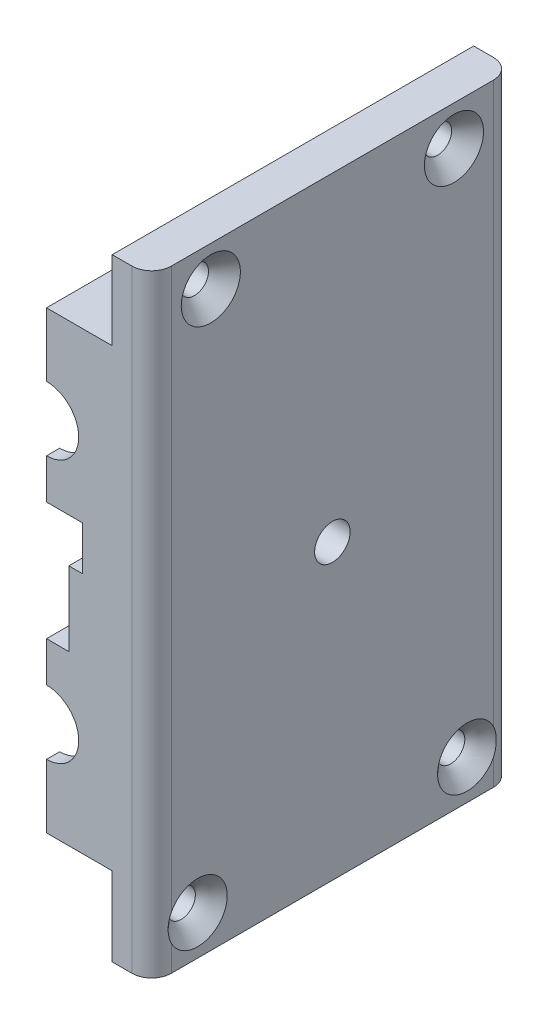
SolidWorks part; units mm, degrees
ref_plane "Front Plane" through (0, 0, 0) normal (0, 0, 1) x (1, 0, 0)
ref_plane "Top Plane" through (0, 0, 0) normal (0, 1, 0) x (1, 0, 0)
ref_plane "Right Plane" through (0, 0, 0) normal (1, 0, 0) x (0, 0, -1)
sketch "Sketch1" plane through (0, 0, 0) normal (0, 0, 1) x (1, 0, 0)
  line L0 (0, 0) -> (0, -93.2)
  line L1 (0, -93.2) -> (-6, -93.2)
  line L2 (-6, -93.2) -> (-6, -81.2)
  line L3 (-6, -81.2) -> (-16, -81.2)
  line L4 (-16, -81.2) -> (-16, -74.2)
  line L5 (-16, -59) -> (-16, -44.3)
  line L6 (-16, -44.3) -> (-10.5, -44.3)
  line L7 (-10.5, -44.3) -> (-10.5, -37.6)
  line L8 (-10.5, -37.6) -> (-16, -37.6)
  line L9 (-16, -37.6) -> (-16, -34.2)
  line L10 (-16, -19) -> (-16, -12)
  line L11 (-16, -12) -> (-6, -12)
  line L12 (-6, -12) -> (-6, 0)
  line L13 (-6, 0) -> (0, 0)
  arc A0 (-16, -74.2) -> (-16, -59) centre (-16, -66.6) ccw
  arc A1 (-16, -34.2) -> (-16, -19) centre (-16, -26.6) ccw
  dimension "D6" = 7.6
  dimension "D7" = 7.6
  dimension "D1" = 6
  dimension "D2" = 12
  dimension "D3" = 12
  dimension "D4" = 14.7
  dimension "D5" = 40
  dimension "D8" = 7
  dimension "D9" = 3.4
  dimension "D10" = 93.2
  dimension "D11" = 10
  dimension "D12" = 10
  dimension "D13" = 5.5
extrude "Boss-Extrude1" add sketch "Sketch1" along normal blind 55
ref_plane "Plane1" through (0, 0, 28.5) normal (0, 0, -1) x (-1, 0, 0)
sketch "Sketch2" plane through (0, 0, 28.5) normal (0, 0, -1) x (-1, 0, 0)
  line L0 (16, -34.2) -> (16, -31.5)
  line L1 (16, -21.7) -> (16, -19)
  arc A0 (16, -19) -> (16, -34.2) centre (16, -26.6) ccw
  arc A1 (16, -21.7) -> (16, -31.5) centre (16, -26.6) ccw
  dimension "D1" = 4.9
extrude "Boss-Extrude2" add sketch "Sketch2" along normal blind 2
sketch "Sketch3" plane through (0, 0, 28.5) normal (0, 0, -1) x (-1, 0, 0)
  line L0 (16, -74.2) -> (16, -71.5)
  line L1 (16, -61.7) -> (16, -59)
  arc A0 (16, -59) -> (16, -74.2) centre (16, -66.6) ccw
  arc A1 (16, -61.7) -> (16, -71.5) centre (16, -66.6) ccw
  dimension "D1" = 4.9
extrude "Boss-Extrude3" add sketch "Sketch3" along normal blind 2
ref_plane "Plane2" through (0, 0, 2) normal (0, 0, -1) x (-1, 0, 0)
sketch "Sketch4" plane through (0, 0, 2) normal (0, 0, -1) x (-1, 0, 0)
  line L1 (16, -59) -> (16, -61.7)
  line L2 (16, -74.2) -> (16, -81.2) construction
  line L4 (16, -71.5) -> (16, -74.2)
  line L5 (16, -19) -> (16, -21.7)
  line L6 (16, -31.5) -> (16, -34.2)
  arc A1 (16, -59) -> (16, -74.2) centre (16, -66.6) ccw construction
  arc A2 (16, -74.2) -> (16, -59) centre (16, -66.6) cw
  arc A4 (16, -61.7) -> (16, -71.5) centre (16, -66.6) ccw
  arc A5 (16, -34.2) -> (16, -19) centre (16, -26.6) cw
  arc A6 (16, -21.7) -> (16, -31.5) centre (16, -26.6) ccw
  dimension "D1" = 4.9
  dimension "D2" = 4.9
extrude "Boss-Extrude5" add sketch "Sketch4" along normal blind 2
ref_plane "Plane3" through (0, 0, 53) normal (0, 0, -1) x (-1, 0, 0)
sketch "Sketch5" plane through (0, 0, 53) normal (0, 0, -1) x (-1, 0, 0)
  line L0 (16, -19) -> (16, -21.7)
  line L1 (16, -31.5) -> (16, -34.2)
  line L2 (16, -59) -> (16, -61.7)
  line L3 (16, -71.5) -> (16, -74.2)
  arc A0 (16, -19) -> (16, -34.2) centre (16, -26.6) ccw construction
  arc A1 (16, -34.2) -> (16, -19) centre (16, -26.6) cw
  arc A2 (16, -21.7) -> (16, -31.5) centre (16, -26.6) ccw
  arc A3 (16, -74.2) -> (16, -59) centre (16, -66.6) cw
  arc A4 (16, -61.7) -> (16, -71.5) centre (16, -66.6) ccw
  dimension "D1" = 4.9
extrude "Boss-Extrude6" add sketch "Sketch5" against normal blind 2
sketch "Sketch7" plane through (0, 0, 55) normal (0, 0, 1) x (1, 0, 0)
  line L1 (-16, -44.3) -> (-12.6, -44.3)
  line L2 (-16, -44.3) -> (-16, -55.6)
  line L3 (-16, -55.6) -> (-12.6, -55.6)
  line L4 (-12.6, -44.3) -> (-12.6, -55.6)
  dimension "D1" = 3.4
  dimension "D2" = 11.3
extrude "Cut-Extrude2" cut sketch "Sketch7" against normal up to surface (55 mm away) up to face at (-10.2, -45.1875, 0)
sketch "Sketch8" plane through (0, 0, 0) normal (1, 0, 0) x (0, 0, -1)
  line L0 (-55, -93.2) -> (-55, 0) construction
  line L1 (0, -93.2) -> (0, 0) construction
  line L2 (-55, 0) -> (0, 0) construction
  line L3 (-55, -93.2) -> (0, -93.2) construction
  circle A0 centre (-46, -6) radius 2.15
  circle A1 centre (-9, -6) radius 2.15
  circle A2 centre (-7, -87.2) radius 2.15
  circle A3 centre (-48, -87.2) radius 2.15
  dimension "D1" = 4.3
  dimension "D2" = 4.3
  dimension "D3" = 4.3
  dimension "D4" = 4.3
  dimension "D5" = 9
  dimension "D6" = 9
  dimension "D7" = 7
  dimension "D8" = 7
  dimension "D9" = 6
  dimension "D10" = 6
  dimension "D11" = 6
  dimension "D12" = 6
extrude "Cut-Extrude3" cut sketch "Sketch8" against normal up to surface (6 mm away) up to face at (-6, -6, 27.5)
sketch "Sketch9" plane through (0, 0, 0) normal (1, 0, 0) x (0, 0, -1)
  line L0 (-55, 0) -> (0, 0) construction
  line L1 (-55, -93.2) -> (-55, 0) construction
  circle A0 centre (-27.5, -48.6) radius 2.7
  dimension "D1" = 5.4
  dimension "D2" = 48.6
  dimension "D3" = 27.5
extrude "Cut-Extrude4" cut sketch "Sketch9" against normal up to surface (12.6 mm away) up to face at (-12.6, -49.95, 27.5)
ref_plane "Plane4" through (-2.5, 0, 0) normal (1, 0, 0) x (0, 0, -1)
sketch "Sketch12" plane through (-2.5, 0, 0) normal (1, 0, 0) x (0, 0, -1)
  circle A0 centre (-46, -6) radius 2.15 construction
  circle A1 centre (-46, -6) radius 2.15
sketch "Sketch13" plane through (0, 0, 0) normal (1, 0, 0) x (0, 0, -1)
  circle A0 centre (-46, -6) radius 4.5
  dimension "D1" = 9
loft "Cut-Loft1" cut profiles "Sketch13", "Sketch12" connector at (0, -9.0908, 49.2707) connector at (-2.5, -7.7977, 47.1793)
pattern_linear "LPattern1" count 2 spacing 37 along (0, 0, -1) of "Cut-Loft1"
sketch "Sketch14" plane through (-2.5, 0, 0) normal (1, 0, 0) x (0, 0, -1)
  circle A0 centre (-48, -87.2) radius 2.15 construction
  circle A1 centre (-48, -87.2) radius 2.15
sketch "Sketch15" plane through (0, 0, 0) normal (1, 0, 0) x (0, 0, -1)
  circle A0 centre (-48, -87.2) radius 4.5
  dimension "D1" = 9
loft "Cut-Loft2" cut profiles "Sketch14", "Sketch15" connector at (-2.5, -88.8038, 46.5681) connector at (0, -88.245, 43.623)
pattern_linear "LPattern2" count 2 spacing 41 along (0, 0, -1) of "Cut-Loft2"
fillet "Fillet1" radius 3 2 edges at (0, -46.6, 0) (0, -46.6, 55)
